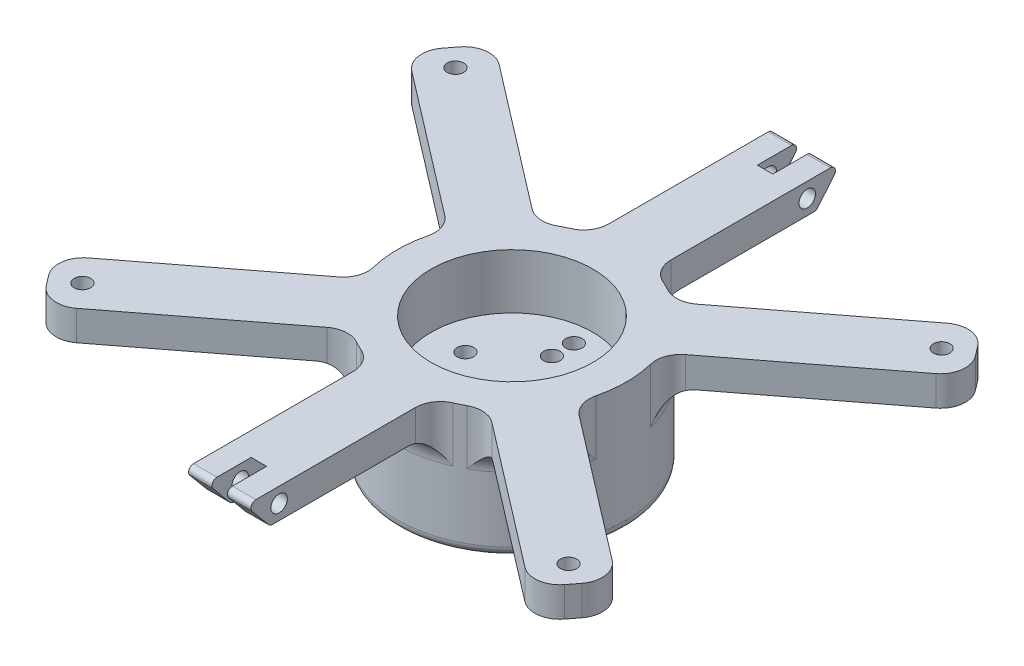
SolidWorks part; units mm, degrees
ref_plane "Front Plane" through (0, 0, 0) normal (0, 0, 1) x (1, 0, 0)
ref_plane "Top Plane" through (0, 0, 0) normal (0, 1, 0) x (1, 0, 0)
ref_plane "Right Plane" through (0, 0, 0) normal (1, 0, 0) x (0, 0, -1)
sketch "Sketch1" plane through (0, 0, 0) normal (0, 1, 0) x (1, 0, 0)
  circle A0 centre (0, 0) radius 23
  dimension "D1" = 46
extrude "Boss-Extrude1" add sketch "Sketch1" along normal mid plane 6
sketch "Sketch2" plane through (0, 0, 0) normal (0, 1, 0) x (1, 0, 0)
  line L0 (-21.3653, 8.5162) -> (-56.5628, 35.5242)
  line L1 (0.2695, -0.2068) -> (-63.7589, 48.924) construction
  line L2 (-48.9532, 45.4411) -> (-13.7557, 18.4331)
  line L3 (0, 37.6664) -> (0, -25.0328) construction
  line L4 (-48.9532, 45.4411) -> (-56.5628, 35.5242)
  circle A0 centre (0, 0) radius 23 construction
  arc A1 (-13.7557, 18.4331) -> (-21.3653, 8.5162) centre (0, 0) ccw
  point P9 (-52.758, 40.4826)
  dimension "D1" = 66.5
  dimension "D2" = 52.5
  dimension "D3" = 12.5
extrude "Boss-Extrude2" add sketch "Sketch2" along normal up to surface and the other way up to surface up to face at (0, 3, 23) other way up to face at (0, -3, 23)
mirror "Mirror1" about plane through (0, 0, 0) normal (1, 0, 0) of "Boss-Extrude2"
mirror "Mirror2" about plane through (0, 0, 0) normal (0, 0, 1) of "Mirror1", "Boss-Extrude2"
sketch "Sketch4" plane through (0, 3, 0) normal (0, 1, 0) x (1, 0, 0)
  line L0 (0, 65.599) -> (0, -44.8835) construction
  line L2 (-6.25, 59.8) -> (6.25, 59.8)
  line L4 (-6.25, 59.8) -> (-6.25, 22.1345)
  line L5 (6.25, 59.8) -> (6.25, 22.1345)
  arc A2 (13.7557, 18.4331) -> (-13.7557, 18.4331) centre (0, 0) ccw construction
  arc A3 (6.25, 22.1345) -> (-6.25, 22.1345) centre (0, 0) ccw
  point P8 (0, 59.8)
  dimension "D1" = 12.5
  dimension "D2" = 59.8
extrude "Boss-Extrude4" add sketch "Sketch4" against normal up to surface (6 mm away)
mirror "Mirror6" about plane through (0, 0, 0) normal (0, 0, 1) of "Boss-Extrude4"
sketch "Sketch3" plane through (0, 3, 0) normal (0, 1, 0) x (1, 0, 0)
  circle A0 centre (-48.7912, 37.4388) radius 1.65
  dimension "D1" = 3.3
  dimension "D2" = 61.5
extrude "Cut-Extrude1" cut sketch "Sketch3" against normal through all
mirror "Mirror3" about plane through (0, 0, 0) normal (1, 0, 0) of "Cut-Extrude1"
mirror "Mirror4" about plane through (0, 0, 0) normal (0, 0, 1) of "Mirror3", "Cut-Extrude1"
sketch "Sketch13" plane through (-6.25, 0, 0) normal (-1, 0, 0) x (0, 0, 1)
  line L0 (-59.8, -3) -> (-59.8, 3) construction
  circle A0 centre (-53, 0) radius 1.65
  point P6 (-59.8, 0)
  dimension "D2" = 3.3
  dimension "D1" = 53
extrude "Cut-Extrude9" cut sketch "Sketch13" against normal blind 14
sketch "Sketch12" plane through (-6.25, 0, 0) normal (-1, 0, 0) x (0, 0, 1)
  line L0 (-59.8, 3) -> (-54.8, -3)
  line L2 (-54.8, -3) -> (-59.8, -3)
  line L3 (-59.8, -3) -> (-59.8, 3)
  line L4 (-22.1345, -3) -> (-59.8, -3) construction
  dimension "D1" = 5
extrude "Cut-Extrude8" cut sketch "Sketch12" against normal up to surface (12.5 mm away) up to face at (6.25, 0, -54.65)
sketch "Sketch14" plane through (0, 3, 0) normal (0, 1, 0) x (1, 0, 0)
  line L0 (-1.55, 59.8) -> (1.55, 59.8)
  line L1 (6.25, 59.8) -> (-6.25, 59.8) construction
  line L2 (1.55, 59.8) -> (1.55, 50.8)
  line L3 (1.55, 50.8) -> (-1.55, 50.8)
  line L4 (-1.55, 50.8) -> (-1.55, 59.8)
  point P4 (0, 50.8)
  dimension "D1" = 9
  dimension "D2" = 3.1
extrude "Cut-Extrude10" cut sketch "Sketch14" against normal blind 14
sketch "Sketch15" plane through (-1.55, 0, 0) normal (1, 0, 0) x (0, 0, -1)
  line L0 (50.8, 3) -> (40.4826, -3)
  line L1 (45.4411, -3) -> (35.5242, -3) construction
  line L2 (40.4826, -3) -> (50.8, -3)
  line L3 (50.8, -3) -> (50.8, 3)
extrude "Cut-Extrude11" cut sketch "Sketch15" along normal up to surface (3.1 mm away) up to face at (1.55, 0, -54.05)
mirror "Mirror8" about plane through (0, 0, 0) normal (0, 0, 1) of "Cut-Extrude11", "Cut-Extrude8", "Cut-Extrude9", "Cut-Extrude10"
sketch "Sketch21" plane through (0, -3, 0) normal (0, -1, 0) x (1, 0, 0)
  circle A0 centre (0, 0) radius 23
extrude "Boss-Extrude7" add sketch "Sketch21" along normal blind 20
sketch "Sketch22" plane through (0, 3, 0) normal (0, 1, 0) x (1, 0, 0)
  circle A0 centre (0, 0) radius 16.25
  dimension "D1" = 32.5
extrude "Cut-Extrude14" cut sketch "Sketch22" against normal blind 11
sketch "Sketch23" plane through (0, -23, 0) normal (0, -1, 0) x (1, 0, 0)
  line L0 (0, 23) -> (0, -23) construction
  line L1 (-23, 0) -> (23, 0) construction
  circle A0 centre (0, 0) radius 12.425 construction
  circle A1 centre (0, 0) radius 8 construction
  circle A2 centre (0, 0) radius 9.35 construction
  arc A3 (6.25, 22.1345) -> (-6.25, 22.1345) centre (0, 0) ccw construction
  arc A4 (-6.25, -22.1345) -> (6.25, -22.1345) centre (0, 0) ccw construction
  circle A5 centre (0, 0) radius 23 construction
  circle A8 centre (0, -8) radius 1.65
  circle A9 centre (0, -12.425) radius 1.65
  circle A10 centre (0, 12.425) radius 1.65
  circle A11 centre (0, 8) radius 1.65
  circle A12 centre (-9.35, 0) radius 1.65
  circle A13 centre (9.35, 0) radius 1.65
  dimension "D1" = 24.85
  dimension "D2" = 18.7
  dimension "D3" = 16
  dimension "D4" = 3.3
  dimension "D5" = 3.3
  dimension "D6" = 3.3
  dimension "D7" = 3.3
extrude "Cut-Extrude15" cut sketch "Sketch23" against normal through all
sketch "Sketch24" plane through (0, -23, 0) normal (0, -1, 0) x (1, 0, 0)
  circle A0 centre (0, 0) radius 3.5
  dimension "D1" = 7
extrude "Cut-Extrude16" cut sketch "Sketch24" against normal blind 4
fillet "Fillet3" radius 5 8 edges at (48.9532, 0, 45.4411) (56.5628, 0, 35.5242) (56.5628, 0, -35.5242) (48.9532, 0, -45.4411) (-48.9532, 0, -45.4411) (-56.5628, 0, -35.5242) (-56.5628, 0, 35.5242) (-48.9532, 0, 45.4411)
fillet "Fillet7" radius 1 8 edges at (3.9, -3, -54.8) (-3.9, -3, -54.8) (-3.9, 3, -59.8) (3.9, -3, 54.8) (-3.9, 3, 59.8) (-3.9, -3, 54.8) (3.9, 3, -59.8) (3.9, 3, 59.8)
fillet "Fillet11" radius 5 13 edges at (-6.25, 0, -22.1345) (-13.7557, 0, -18.4331) (-21.3653, 0, -8.5162) (-21.3653, 0, 8.5162) (-13.7557, 0, 18.4331) (-6.25, 0, 22.1345) (6.25, 0, 22.1345) (13.7557, 0, 18.4331) (21.3653, 0, 8.5162) (21.3653, 0, -8.5162) (13.7557, 0, -18.4331) (6.25, 0, -22.1345) (18.2471, -3, 14.0015)
fillet "Fillet12" radius 2 1 edges at (0, -23, -23)
